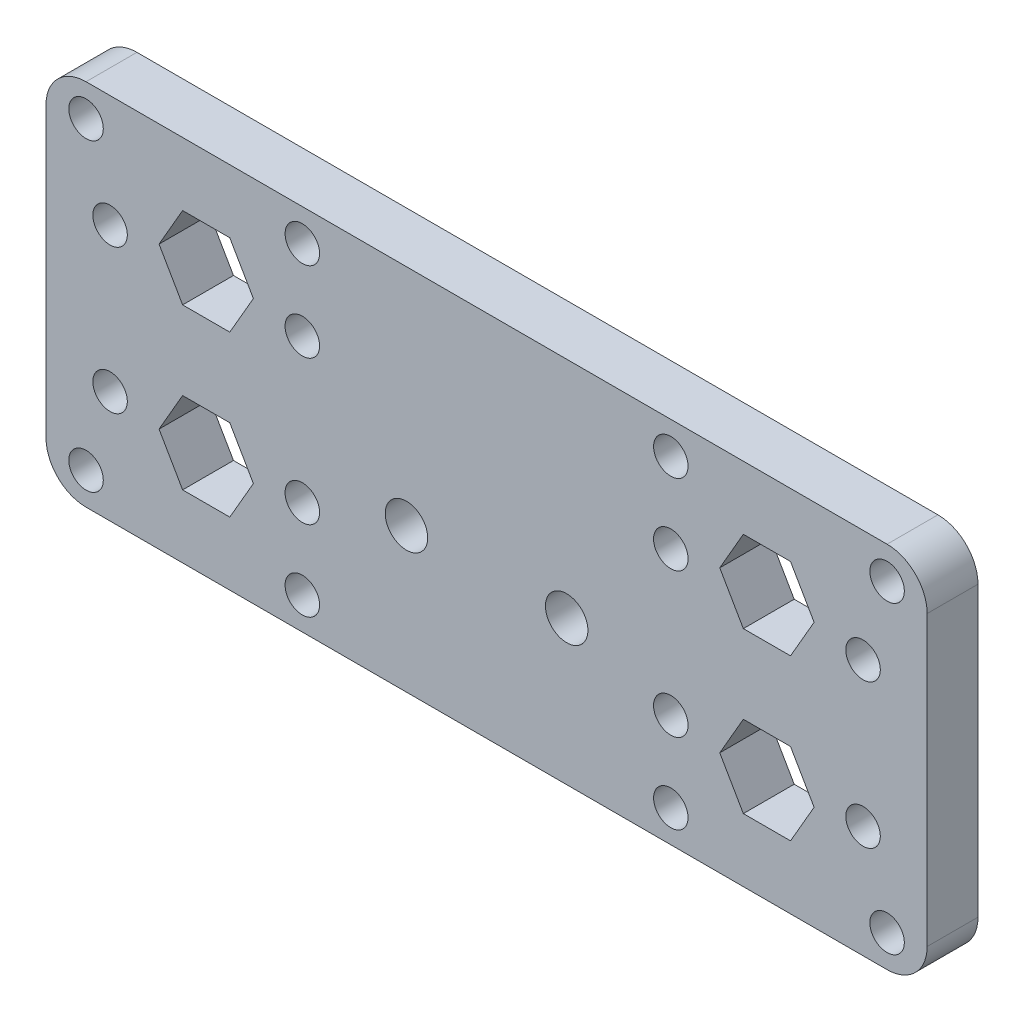
SolidWorks part; units mm, degrees
ref_plane "Front Plane" through (0, 0, 0) normal (0, 0, 1) x (1, 0, 0)
ref_plane "Top Plane" through (0, 0, 0) normal (0, 1, 0) x (1, 0, 0)
ref_plane "Right Plane" through (0, 0, 0) normal (1, 0, 0) x (0, 0, -1)
sketch "Sketch1" plane through (0, 0, 0) normal (0, 0, 1) x (1, 0, 0)
  line L0 (-55, -23) -> (-55, 23)
  line L1 (-55, -23) -> (55, -23)
  line L2 (-55, 23) -> (55, 23)
  line L3 (55, -23) -> (55, 23)
  line L4 (-55, -23) -> (55, 23) construction
  line L5 (-55, 23) -> (55, -23) construction
  point P1 (0, 0)
  dimension "D1" = 46
  dimension "D2" = 110
extrude "Boss-Extrude1" add sketch "Sketch1" along normal blind 6.35
sketch "Sketch2" plane through (0, 0, 6.35) normal (0, 0, 1) x (1, 0, 0)
  line L0 (-35, -10) -> (-35, 10) construction
  line L1 (-35, -10) -> (35, -10) construction
  line L2 (-35, 10) -> (35, 10) construction
  line L3 (35, -10) -> (35, 10) construction
  line L4 (-35, -10) -> (35, 10) construction
  line L5 (-35, 10) -> (35, -10) construction
  line L7 (-32.0555, 15.1) -> (-37.9445, 15.1)
  line L8 (-37.9445, 15.1) -> (-40.889, 10)
  line L9 (-40.889, 10) -> (-37.9445, 4.9)
  line L10 (-37.9445, 4.9) -> (-32.0555, 4.9)
  line L11 (-32.0555, 4.9) -> (-29.111, 10)
  line L12 (-29.111, 10) -> (-32.0555, 15.1)
  line L13 (37.9445, 15.1) -> (32.0555, 15.1)
  line L14 (32.0555, 15.1) -> (29.111, 10)
  line L15 (29.111, 10) -> (32.0555, 4.9)
  line L16 (32.0555, 4.9) -> (37.9445, 4.9)
  line L17 (37.9445, 4.9) -> (40.889, 10)
  line L18 (40.889, 10) -> (37.9445, 15.1)
  line L19 (37.9445, -4.9) -> (32.0555, -4.9)
  line L20 (32.0555, -4.9) -> (29.111, -10)
  line L21 (29.111, -10) -> (32.0555, -15.1)
  line L22 (32.0555, -15.1) -> (37.9445, -15.1)
  line L23 (37.9445, -15.1) -> (40.889, -10)
  line L24 (40.889, -10) -> (37.9445, -4.9)
  line L25 (-32.0555, -4.9) -> (-37.9445, -4.9)
  line L26 (-37.9445, -4.9) -> (-40.889, -10)
  line L27 (-40.889, -10) -> (-37.9445, -15.1)
  line L28 (-37.9445, -15.1) -> (-32.0555, -15.1)
  line L29 (-32.0555, -15.1) -> (-29.111, -10)
  line L30 (-29.111, -10) -> (-32.0555, -4.9)
  circle A0 centre (-35, 10) radius 5.1 construction
  circle A1 centre (35, 10) radius 5.1 construction
  circle A2 centre (35, -10) radius 5.1 construction
  circle A3 centre (-35, -10) radius 5.1 construction
  point P1 (0, 0)
  dimension "D1" = 70
  dimension "D2" = 20
  dimension "D3" = 10.2
  dimension "D4" = 2
  dimension "D5" = 2
extrude "Cut-Extrude1" cut sketch "Sketch2" against normal through all
sketch "Sketch4" plane through (0, 0, 0) normal (0, 0, -1) x (-1, 0, 0)
  line L0 (-32.0555, -15.1) -> (-37.9445, -15.1) construction
  line L1 (-47, 9) -> (-23, 9) construction
  line L2 (-47, 9) -> (-47, -9) construction
  line L3 (-47, -9) -> (-23, -9) construction
  line L4 (-23, 9) -> (-23, -9) construction
  line L5 (0, 23) -> (0, -23) construction
  line L6 (-55, 23) -> (55, 23) construction
  line L7 (55, -23) -> (-55, -23) construction
  line L8 (47, 9) -> (47, -9) construction
  line L9 (47, 9) -> (23, 9) construction
  line L10 (23, 9) -> (23, -9) construction
  line L11 (47, -9) -> (23, -9) construction
  point P4 (-23, 0)
  point P5 (-35, -9)
  point P7 (-35, -15.1)
  dimension "D1" = 18
  dimension "D2" = 24
hole_wizard "#8 Clearance Hole2" positions "Sketch6" profile "Sketch5" hole size "#8" standard "ANSI Inch" end condition through all
sketch "Sketch6" plane through (0, 0, 0) normal (0, 0, -1) x (-1, 0, 0)
  point P0 (-47, 9)
  point P3 (-23, 9)
  point P6 (-23, -9)
  point P9 (-47, -9)
  point P12 (23, -9)
  point P15 (23, 9)
  point P18 (47, 9)
  point P21 (47, -9)
sketch "Sketch5" plane through (47, 9, 0) normal (1, 0, 0) x (0, 1, 0)
  line L0 (0, 0) -> (0, 6.35)
  line L1 (0, 6.35) -> (2.1526, 6.35)
  line L2 (2.1526, 6.35) -> (2.1526, 0)
  line L5 (2.1526, 0) -> (0, 0)
  line L11 (0, -6.35) -> (0, 107.95) construction
  dimension "Thru Hole Dia." = 4.3053
  dimension "Thru Hole Depth" = 6.35
fillet "Fillet1" radius 5 4 edges at (-55, 23, 3.175) (-55, -23, 3.175) (55, -23, 3.175) (55, 23, 3.175)
sketch "Sketch7" plane through (0, 0, 6.35) normal (0, 0, 1) x (1, 0, 0)
  line L0 (-10, -5) -> (10, -5) construction
  point P0 (0, 0)
  point P4 (0, -5)
  dimension "D1" = 20
  dimension "D2" = 5
hole_wizard "M5 Clearance Hole1" positions "Sketch9" profile "Sketch8" hole size "M5" standard "ANSI Metric" end condition through all
sketch "Sketch9" plane through (0, 0, 6.35) normal (0, 0, 1) x (1, 0, 0)
  point P0 (-10, -5)
  point P3 (10, -5)
sketch "Sketch8" plane through (-10, -5, 6.35) normal (1, 0, 0) x (0, -1, 0)
  line L0 (0, 0) -> (0, 6.35)
  line L1 (0, 6.35) -> (2.65, 6.35)
  line L2 (2.65, 6.35) -> (2.65, 0)
  line L5 (2.65, 0) -> (0, 0)
  line L11 (0, -6.35) -> (0, 107.95) construction
  dimension "Thru Hole Dia." = 5.3
  dimension "Thru Hole Depth" = 6.35
sketch "Sketch10" plane through (0, 0, 6.35) normal (0, 0, 1) x (1, 0, 0)
  line L1 (-23, -19) -> (23, -19) construction
  line L2 (-23, -19) -> (-23, 19) construction
  line L3 (-23, 19) -> (23, 19) construction
  line L4 (23, -19) -> (23, 19) construction
  line L5 (-23, -19) -> (23, 19) construction
  line L6 (-23, 19) -> (23, -19) construction
  line L7 (-50, -19) -> (50, -19) construction
  line L8 (-50, -19) -> (-50, 19) construction
  line L9 (-50, 19) -> (50, 19) construction
  line L10 (50, -19) -> (50, 19) construction
  line L11 (-50, -19) -> (50, 19) construction
  line L12 (-50, 19) -> (50, -19) construction
  point P0 (0, 0)
  point P6 (0, 0)
  dimension "D1" = 46
  dimension "D2" = 38
  dimension "D3" = 38
  dimension "D4" = 100
hole_wizard "#8 Clearance Hole1" positions "Sketch12" profile "Sketch11" hole size "#8" standard "ANSI Inch" end condition through all
sketch "Sketch12" plane through (0, 0, 6.35) normal (0, 0, 1) x (1, 0, 0)
  point P0 (-23, 19)
  point P3 (-23, -19)
  point P6 (23, -19)
  point P9 (23, 19)
  point P13 (-50, 19)
  point P16 (-50, -19)
  point P19 (50, -19)
  point P22 (50, 19)
sketch "Sketch11" plane through (-23, 19, 6.35) normal (1, 0, 0) x (0, -1, 0)
  line L0 (0, 0) -> (0, 6.35)
  line L1 (0, 6.35) -> (2.1526, 6.35)
  line L2 (2.1526, 6.35) -> (2.1526, 0)
  line L5 (2.1526, 0) -> (0, 0)
  line L11 (0, -6.35) -> (0, 107.95) construction
  dimension "Thru Hole Dia." = 4.3053
  dimension "Thru Hole Depth" = 6.35
